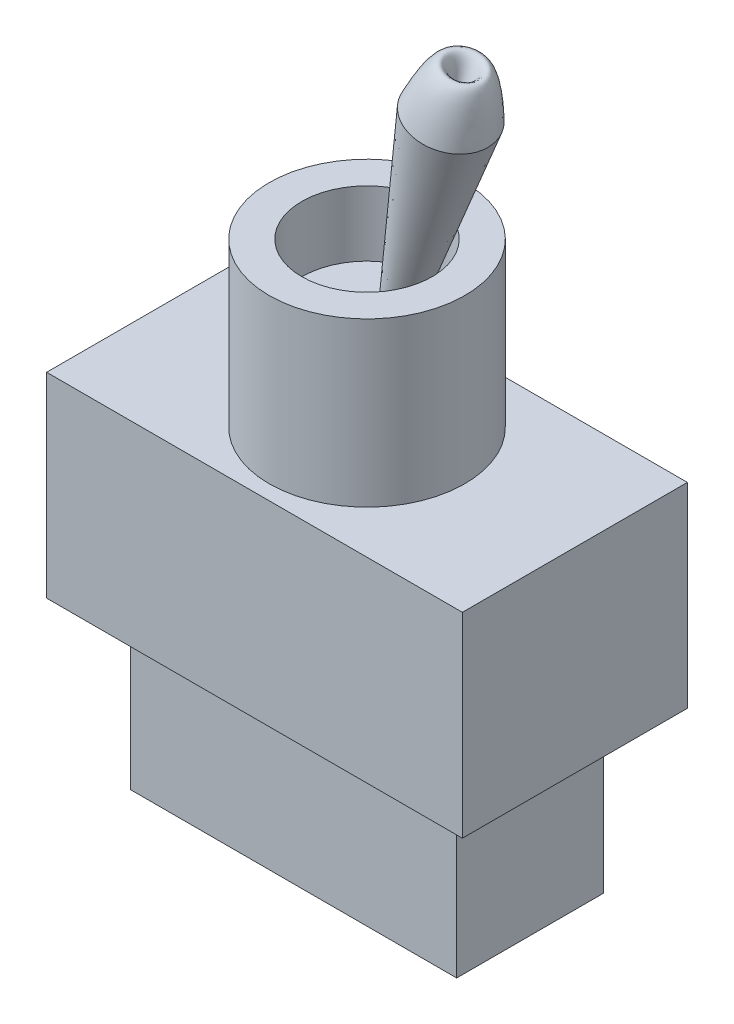
SolidWorks part; units mm, degrees
ref_plane "Płaszczyzna przednia" through (0, 0, 0) normal (0, 0, 1) x (1, 0, 0)
ref_plane "Płaszczyzna górna" through (0, 0, 0) normal (0, 1, 0) x (1, 0, 0)
ref_plane "Płaszczyzna prawa" through (0, 0, 0) normal (1, 0, 0) x (0, 0, -1)
sketch "Szkic1" plane through (0, 0, 0) normal (0, 1, 0) x (1, 0, 0)
  line L1 (12.75, -6.9) -> (-12.75, -6.9)
  line L2 (12.75, -6.9) -> (12.75, 6.9)
  line L3 (12.75, 6.9) -> (-12.75, 6.9)
  line L4 (-12.75, -6.9) -> (-12.75, 6.9)
  line L5 (12.75, -6.9) -> (-12.75, 6.9) construction
  line L6 (12.75, 6.9) -> (-12.75, -6.9) construction
  point P0 (0, 0)
  dimension "D1" = 13.8
  dimension "D2" = 25.5
extrude "Dodanie-wyciągnięcie1" add sketch "Szkic1" along normal blind 12
sketch "Szkic2" plane through (0, 12, 0) normal (0, 1, 0) x (1, 0, 0)
  circle A0 centre (0, 0) radius 6
extrude "Dodanie-wyciągnięcie2" add sketch "Szkic2" along normal blind 10
sketch "Szkic4" plane through (0, 22, 0) normal (0, 1, 0) x (1, 0, 0)
  circle A0 centre (0, 0) radius 4
extrude "Wytnij-wyciągnięcie1" cut sketch "Szkic4" against normal blind 4
sketch "Szkic3" plane through (0, 0, 0) normal (0, 0, 1) x (1, 0, 0)
  line L0 (0, 12) -> (0, 0) construction
  line L1 (0, 12) -> (5.1764, 31.3185) construction
  line L2 (0, 12) -> (2.8637, 31.7939)
  line L3 (0, 12) -> (5.1764, 31.3185)
  spline S0 degree 3 poles (5.1764, 31.3185) (5.509, 35.1066) (4.8412, 35.6273) (2.8637, 31.7939) knots 0 0 0 0 1 1 1 1
  dimension "D1" = 12
  dimension "D2" = 15
  dimension "D3" = 20
  dimension "D4" = 20
revolve "Obrót1" add sketch "Szkic3" angle 360 about L3
sketch "Szkic5" plane through (0, 0, 0) normal (0, -1, 0) x (1, 0, 0)
  line L1 (10, 4.5) -> (-10, 4.5)
  line L2 (10, 4.5) -> (10, -4.5)
  line L3 (10, -4.5) -> (-10, -4.5)
  line L4 (-10, 4.5) -> (-10, -4.5)
  line L5 (10, 4.5) -> (-10, -4.5) construction
  line L6 (10, -4.5) -> (-10, 4.5) construction
  point P0 (0, 0)
  dimension "D1" = 9
  dimension "D2" = 20
extrude "Dodanie-wyciągnięcie3" add sketch "Szkic5" along normal blind 10
